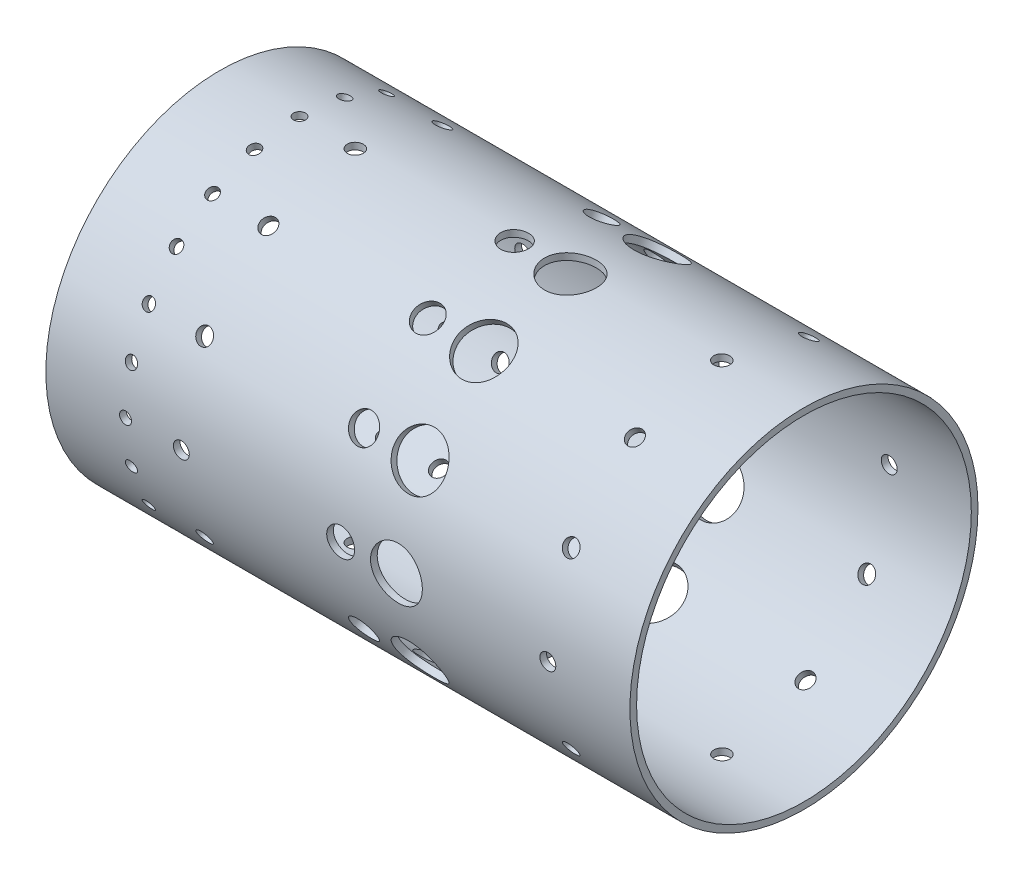
SolidWorks part; units mm, degrees
ref_plane "Front Plane" through (0, 0, 0) normal (0, 0, 1) x (1, 0, 0)
ref_plane "Top Plane" through (0, 0, 0) normal (0, 1, 0) x (1, 0, 0)
ref_plane "Right Plane" through (0, 0, 0) normal (1, 0, 0) x (0, 0, -1)
sketch "Sketch1" plane through (0, 0, 0) normal (1, 0, 0) x (0, 0, -1)
  circle A0 centre (0, 0) radius 21.0058
  circle A1 centre (0, 0) radius 21.844
  dimension "D1" = 43.688
  dimension "D2" = 0.8382
extrude "Boss-Extrude1" add sketch "Sketch1" along normal blind 73.3044
sketch "Sketch3" plane through (0, 0, 0) normal (0, 1, 0) x (1, 0, 0)
  line L0 (0, 0) -> (79.3536, 0) construction
sketch "Sketch4" plane through (0, 0, 0) normal (0, 1, 0) x (1, 0, 0)
  line L0 (0, 0) -> (79.3536, 0) construction
  circle A0 centre (10, 0) radius 0.75
  dimension "D2" = 1.5
  dimension "D1" = 10
extrude "Cut-Extrude1" cut sketch "Sketch4" against normal through all
pattern_circular "CirPattern1" count 24 over 360 about axis through (0, 0, 0) along (1, 0, 0) of "Cut-Extrude1"
sketch "Sketch5" plane through (0, 0, 0) normal (0, 1, 0) x (1, 0, 0)
  line L0 (0, 0) -> (79.3536, 0) construction
  line L1 (0, 21.844) -> (0, -21.844) construction
  circle A0 centre (17, 0) radius 1
  dimension "D2" = 2
  dimension "D1" = 17
extrude "Cut-Extrude3" cut sketch "Sketch5" against normal through all
pattern_circular "CirPattern2" count 12 over 360 about axis through (0, 0, 0) along (1, 0, 0) of "Cut-Extrude3"
sketch "Sketch6" plane through (0, 0, 0) normal (0, 1, 0) x (1, 0, 0)
  line L0 (0, 0) -> (79.3536, 0) construction
  line L1 (0, 21.844) -> (0, -21.844) construction
  circle A0 centre (37, 0) radius 1.75
  dimension "D2" = 3.5
  dimension "D1" = 37
extrude "Cut-Extrude4" cut sketch "Sketch6" against normal through all
pattern_circular "CirPattern3" count 12 over 360 about axis through (0, 0, 0) along (1, 0, 0) of "Cut-Extrude4"
sketch "Sketch7" plane through (0, 0, 0) normal (0, 1, 0) x (1, 0, 0)
  line L0 (0, 0) -> (79.3536, 0) construction
  circle A0 centre (44, 0) radius 3.25
  dimension "D2" = 6.5
  dimension "D1" = 44
extrude "Cut-Extrude5" cut sketch "Sketch7" against normal through all
pattern_circular "CirPattern5" count 12 over 360 about axis through (0, 0, 0) along (1, 0, 0) of "Cut-Extrude5"
sketch "Sketch8" plane through (0, 0, 0) normal (0, 0, 1) x (1, 0, 0)
  line L0 (0, 0) -> (79.3536, 0) construction
  circle A0 centre (63, 0) radius 1
  dimension "D1" = 2
  dimension "D2" = 63
extrude "Cut-Extrude6" cut sketch "Sketch8" against normal through all
pattern_circular "CirPattern6" count 12 over 360 about axis through (0, 0, 0) along (1, 0, 0) of "Cut-Extrude6"
